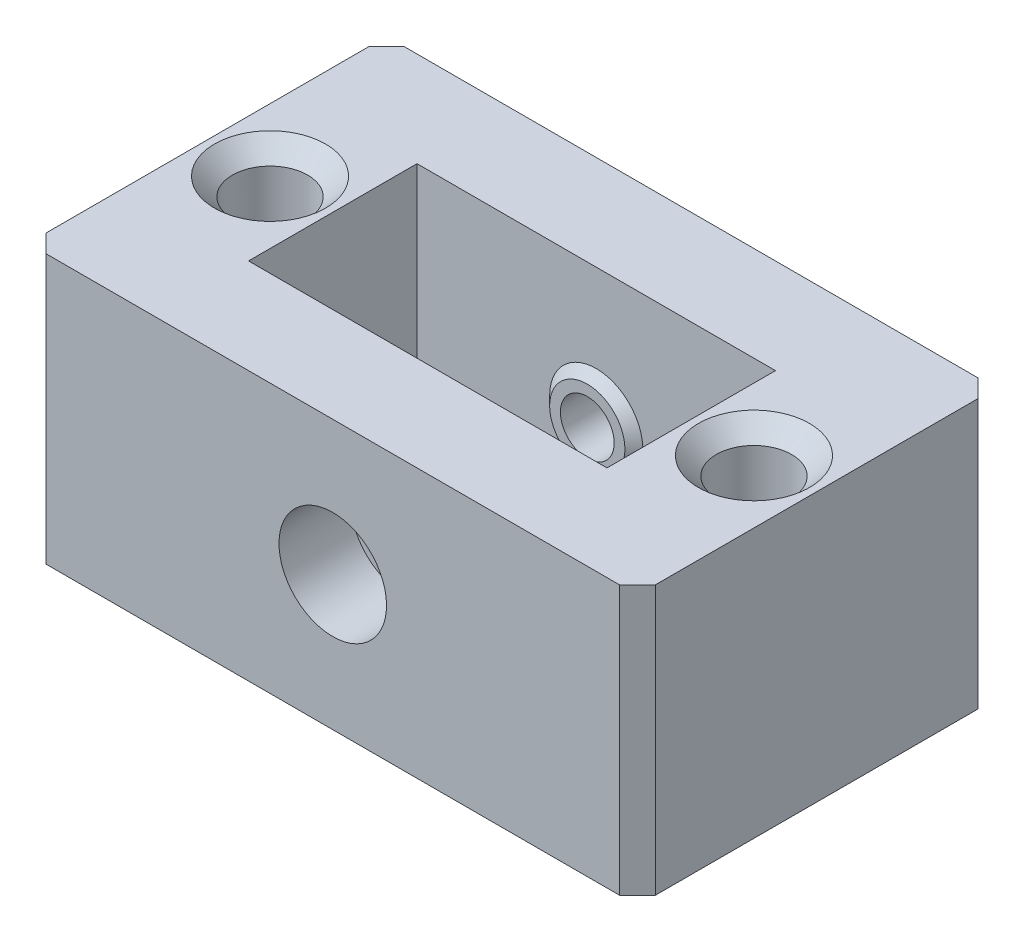
SolidWorks part; units mm, degrees
ref_plane "Front Plane" through (0, 0, 0) normal (0, 0, 1) x (1, 0, 0)
ref_plane "Top Plane" through (0, 0, 0) normal (0, 1, 0) x (1, 0, 0)
ref_plane "Right Plane" through (0, 0, 0) normal (1, 0, 0) x (0, 0, -1)
sketch "Sketch1" plane through (0, 0, 0) normal (0, 1, 0) x (1, 0, 0)
  line L1 (-17, -10) -> (17, -10)
  line L2 (-17, -10) -> (-17, 10)
  line L3 (-17, 10) -> (17, 10)
  line L4 (17, -10) -> (17, 10)
  line L5 (-17, -10) -> (17, 10) construction
  line L6 (-17, 10) -> (17, -10) construction
  point P0 (0, 0)
  dimension "D1" = 34
  dimension "D2" = 20
extrude "Boss-Extrude1" add sketch "Sketch1" along normal blind 15
sketch "Sketch3" plane through (0, 15, 0) normal (0, 1, 0) x (1, 0, 0)
  line L8 (-10, -4.7) -> (10, -4.7)
  line L9 (-10, -4.7) -> (-10, 4.7)
  line L10 (-10, 4.7) -> (10, 4.7)
  line L11 (10, -4.7) -> (10, 4.7)
  line L12 (-10, -4.7) -> (10, 4.7) construction
  line L13 (-10, 4.7) -> (10, -4.7) construction
  point P0 (0, 0)
  dimension "D1" = 9.4
  dimension "D2" = 20
extrude "Cut-Extrude1" cut sketch "Sketch3" against normal blind 20
sketch "Sketch8" plane through (0, 0, -10) normal (0, 0, -1) x (-1, 0, 0)
  line L0 (-17, 7.5) -> (17, 7.5) construction
  line L1 (17, 15) -> (17, 0) construction
  line L2 (-17, 15) -> (-17, 0) construction
  circle A0 centre (0, 7.5) radius 1.5
  dimension "D1" = 3
extrude "Cut-Extrude6" cut sketch "Sketch8" against normal through all
sketch "Sketch9" plane through (0, 0, 10) normal (0, 0, 1) x (1, 0, 0)
  circle A0 centre (0, 7.5) radius 3
  dimension "D1" = 6
extrude "Cut-Extrude7" cut sketch "Sketch9" against normal blind 4
sketch "Sketch11" plane through (0, 0, -4.7) normal (0, 0, 1) x (1, 0, 0)
  circle A0 centre (0, 7.5) radius 2.1
  circle A1 centre (0, 7.5) radius 1.5
  dimension "D1" = 0.6
extrude "Boss-Extrude2" add sketch "Sketch11" along normal blind 0.5
sketch "Sketch12" plane through (0, 0, 4.7) normal (0, 0, -1) x (-1, 0, 0)
  circle A0 centre (0, 7.5) radius 2.1
  circle A1 centre (0, 7.5) radius 1.5
  dimension "D1" = 0.6
extrude "Boss-Extrude3" add sketch "Sketch12" along normal blind 0.5
chamfer "Chamfer5" distance 0.5 angle 45 2 edges at (2.1, 7.5, 4.7) (-2.1, 7.5, -4.7)
sketch "Sketch13" plane through (0, 15, 0) normal (0, 1, 0) x (1, 0, 0)
  line L0 (-17, 0) -> (17, 0) construction
  line L1 (-17, 10) -> (-17, -10) construction
  line L2 (17, -10) -> (17, 10) construction
  circle A0 centre (-13.5, 0) radius 2.1
  circle A1 centre (13.5, 0) radius 2.1
  dimension "D1" = 4.2
  dimension "D2" = 3.5
  dimension "D3" = 3.5
extrude "Cut-Extrude8" cut sketch "Sketch13" against normal through all
chamfer "Chamfer6" distance 1 angle 45 2 edges at (13.5, 15, 2.1) (-13.5, 15, 2.1)
chamfer "Chamfer7" distance 1 angle 45 4 edges at (17, 7.5, 10) (-17, 7.5, 10) (-17, 7.5, -10) (17, 7.5, -10)
